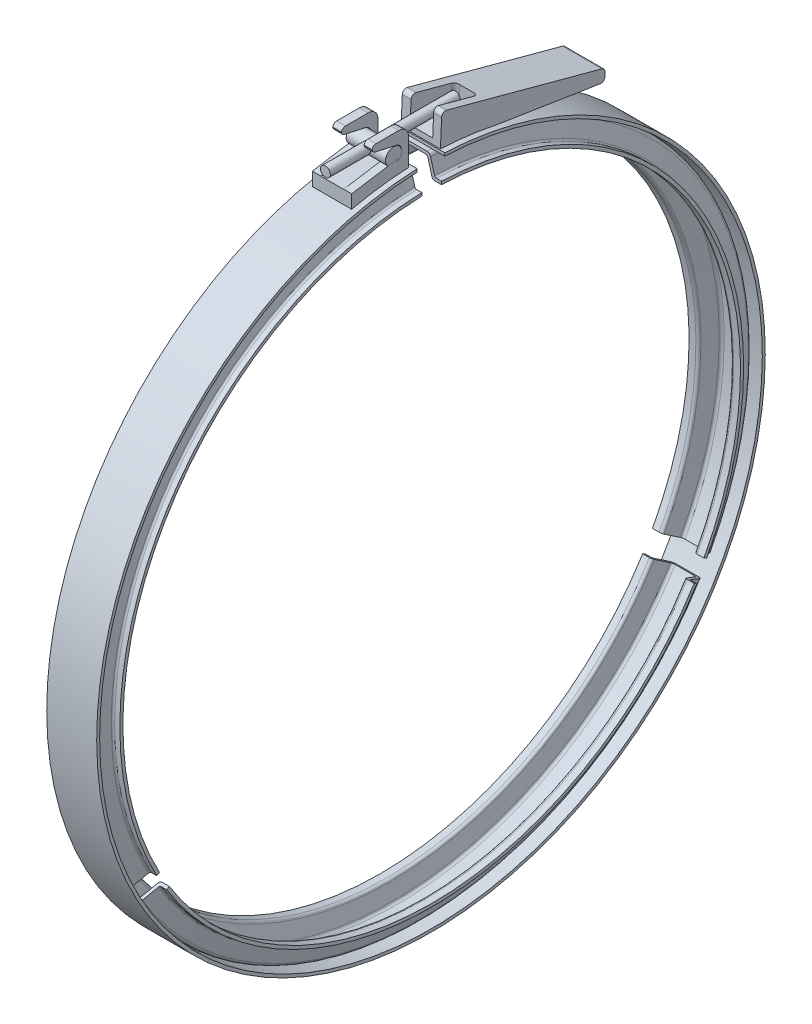
SolidWorks part; units mm, degrees
ref_plane "Front Plane" through (0, 0, 0) normal (0, 0, 1) x (1, 0, 0)
ref_plane "Top Plane" through (0, 0, 0) normal (0, 1, 0) x (1, 0, 0)
ref_plane "Right Plane" through (0, 0, 0) normal (1, 0, 0) x (0, 0, -1)
sketch "Sketch1" plane through (0, 0, 0) normal (1, 0, 0) x (0, 0, -1)
  circle A0 centre (0, 0) radius 166.56
  dimension "D1" = 333.12
sketch "Sketch2" plane through (0, 0, 0) normal (0, 0, 1) x (1, 0, 0)
  line L0 (-4.754, -166.56) -> (4.754, -166.56)
  line L1 (0, 0) -> (0, -217.2607) construction
  line L2 (-13.08, -157.04) -> (-13.08, -158.61)
  line L3 (13.08, -157.04) -> (13.08, -158.61)
  line L4 (0, -166.56) -> (0, 166.56) construction
  line L5 (6.2029, -165.4482) -> (8.158, -158.1518)
  line L6 (-13.08, -158.61) -> (-10.4279, -158.61)
  line L7 (9.462, -159.3512) -> (7.5069, -166.6476)
  line L8 (5.575, -168.13) -> (-5.575, -168.13)
  line L9 (-6.2029, -165.4482) -> (-8.158, -158.1518)
  line L10 (10.4279, -158.61) -> (13.08, -158.61)
  line L11 (-9.462, -159.3512) -> (-7.5069, -166.6476)
  line L12 (-13.08, -157.04) -> (-9.6069, -157.04)
  line L13 (9.6069, -157.04) -> (13.08, -157.04)
  arc A0 (-6.2029, -165.4482) -> (-4.754, -166.56) centre (-4.754, -165.06) ccw
  arc A1 (6.2029, -165.4482) -> (4.754, -166.56) centre (4.754, -165.06) cw
  arc A2 (-7.5069, -166.6476) -> (-5.575, -168.13) centre (-5.575, -166.13) ccw
  arc A3 (7.5069, -166.6476) -> (5.575, -168.13) centre (5.575, -166.13) cw
  arc A4 (-9.462, -159.3512) -> (-10.4279, -158.61) centre (-10.4279, -159.61) ccw
  arc A5 (-8.158, -158.1518) -> (-9.6069, -157.04) centre (-9.6069, -158.54) ccw
  arc A6 (9.6069, -157.04) -> (8.158, -158.1518) centre (9.6069, -158.54) ccw
  arc A7 (10.4279, -158.61) -> (9.462, -159.3512) centre (10.4279, -159.61) ccw
  point P7 (0, -166.56)
  point P17 (-5.905, -166.56)
  point P20 (5.905, -166.56)
  point P33 (-8.4559, -157.04)
  point P36 (8.4559, -157.04)
  dimension "D9" = 1.5
  dimension "D10" = 2
  dimension "D16" = 1
  dimension "D17" = 1.5
  dimension "D18" = 1.5
  dimension "D19" = 1
  dimension "D1" = 11.81
  dimension "D2" = 5.905
  dimension "D3" = 30
  dimension "D4" = 15
  dimension "D5" = 1.57
  dimension "D6" = 1.57
  dimension "D7" = 1.57
  dimension "D8" = 1.57
  dimension "D11" = 9.52
  dimension "D12" = 15
  dimension "D13" = 26.16
  dimension "D14" = 13.08
  dimension "D15" = 1.57
sweep "Sweep1" add profiles "Sketch2" path "Sketch1"
sketch "Sketch3" plane through (0, 0, 0) normal (1, 0, 0) x (0, 0, -1)
  line L0 (0, 0) -> (0, 224.6146) construction
  line L1 (-5, 175.4276) -> (5, 175.4276)
  line L2 (-5, 175.4276) -> (-5, 2.8868)
  line L4 (5, 175.4276) -> (5, 2.8868)
  line L5 (-5, 2.8868) -> (-182.9307, -99.8416)
  line L6 (-182.9307, -99.8416) -> (-177.9307, -108.5019)
  line L7 (-177.9307, -108.5019) -> (-5, -8.6603)
  line L8 (5, 2.8868) -> (190.606, -104.2729)
  line L9 (190.606, -104.2729) -> (185.606, -112.9332)
  line L10 (185.606, -112.9332) -> (5, -8.6603)
  line L11 (0, 0) -> (-180.4307, -104.1717) construction
  line L12 (0, 0) -> (188.106, -108.6031) construction
  line L13 (-5, -8.6603) -> (5, -8.6603)
  dimension "D1" = 10
  dimension "D2" = 5
  dimension "D3" = 10
  dimension "D4" = 10
  dimension "D5" = 120
  dimension "D6" = 120
  dimension "D7" = 5
  dimension "D8" = 5
extrude "Extrude1" cut sketch "Sketch3" against normal mid plane 40
sketch "Sketch4" plane through (0, 0, 0) normal (1, 0, 0) x (0, 0, -1)
  line L0 (0, 186.8251) -> (0, -203.9787) construction
  line L1 (-7, 169.8558) -> (-7, 168.3545)
  line L5 (7, 169.8558) -> (7, 168.3545)
  arc A0 (-7, 168.3545) -> (7, 168.3545) centre (0, 0) ccw
  arc A1 (-7, 169.8558) -> (7, 169.8558) centre (0, 0) ccw
  circle A2 centre (0, 0) radius 170 construction
  circle A3 centre (0, 0) radius 168.5 construction
  dimension "D2" = 1.5
  dimension "D3" = 14
  dimension "D4" = 7
  dimension "D1" = 337
extrude "Extrude6" add sketch "Sketch4" along normal mid plane 25.4
sketch "Sketch6" plane through (0, 0, 0) normal (1, 0, 0) x (0, 0, -1)
  line L0 (7.5086, 169.9724) -> (8.2211, 186.1018)
  line L1 (8.2211, 186.1018) -> (91.1614, 163.7616)
  line L2 (91.1614, 163.7616) -> (91.1614, 157.6505)
  line L3 (91.1614, 157.6505) -> (35.4138, 166.4117)
  line L4 (-8.72, 169.9146) -> (-8.72, 188.6667)
  line L5 (-8.72, 188.6667) -> (-27.2757, 188.6667)
  line L6 (-27.2757, 188.6667) -> (-27.2757, 185.5473)
  line L7 (-27.2757, 185.5473) -> (-14.9764, 182.8306)
  line L9 (-13.8669, 176.5544) -> (-37.6125, 172.7545)
  line L10 (-37.6125, 172.7545) -> (-37.6125, 165.9286)
  arc A0 (35.4138, 166.4117) -> (7.5086, 169.9724) centre (0, 0) ccw
  arc A1 (-8.72, 169.9146) -> (-37.6125, 165.9286) centre (0, 0) ccw
  arc A2 (-14.9764, 182.8306) -> (-13.8669, 176.5544) centre (-15.7203, 179.4629) cw
extrude "Extrude7" add sketch "Sketch6" along normal mid plane 20
sketch "Sketch7" plane through (0, 188.6667, 0) normal (0, 1, 0) x (1, 0, 0)
  line L1 (-5.5403, 30.6414) -> (5.9469, 30.6414)
  line L2 (-5.5403, 30.6414) -> (-5.5403, -44.1838)
  line L3 (-5.5403, -44.1838) -> (5.9469, -44.1838)
  line L4 (5.9469, 30.6414) -> (5.9469, -44.1838)
extrude "Extrude8" cut sketch "Sketch7" against normal blind 16
shell "Shell1" thickness 2 removed face at (0, 162.0311, -63.2876)
fillet "Fillet3" radius 2 4 edges at (-7.7702, 188.6667, 27.2757) (7.9734, 188.6667, 27.2757) (7.9734, 185.5473, 27.2757) (-7.7702, 185.5473, 27.2757)
fillet "Fillet4" radius 5 2 edges at (-7.7702, 188.6667, 8.72) (7.9734, 188.6667, 8.72)
ref_plane "Plane1" through (0, 0, -25) normal (0, 0, 1) x (1, 0, 0)
fillet "Fillet5" radius 2 4 edges at (0, 157.6505, -91.1614) (0, 163.7616, -91.1614) (7.9734, 186.1018, -8.2211) (-7.7702, 186.1018, -8.2211)
fillet "Fillet6" radius 2 2 edges at (-5.5403, 176.3648, -30.6414) (5.9469, 176.3648, -30.6414)
sketch "Sketch8" plane through (0, 0, -25) normal (0, 0, 1) x (1, 0, 0)
  circle A0 centre (0, 179.2515) radius 2.5192
extrude "Extrude9" add sketch "Sketch8" along normal blind 66
sketch "Sketch9" plane through (-10, 0, 0) normal (-1, 0, 0) x (0, 0, 1)
  circle A0 centre (16.3237, 178.7483) radius 4.1174
extrude "Extrude10" add sketch "Sketch9" against normal blind 20
